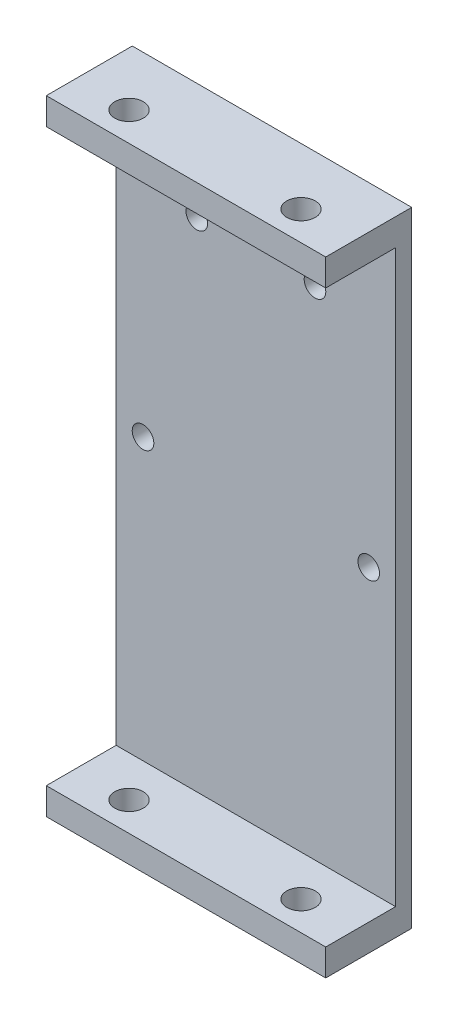
SolidWorks part; units mm, degrees
ref_plane "Front Plane" through (0, 0, 0) normal (0, 0, 1) x (1, 0, 0)
ref_plane "Top Plane" through (0, 0, 0) normal (0, 1, 0) x (1, 0, 0)
ref_plane "Right Plane" through (0, 0, 0) normal (1, 0, 0) x (0, 0, -1)
sketch "Sketch1" plane through (0, 0, 0) normal (0, 0, 1) x (1, 0, 0)
  line L0 (66.04, 78.728) -> (66.04, 66.282) construction
  line L1 (0, 0) -> (66.04, 0)
  line L2 (0, 0) -> (0, 147.574)
  line L3 (0, 147.574) -> (66.04, 147.574)
  line L4 (66.04, 0) -> (66.04, 147.574)
  dimension "D2" = 147.574
extrude "Boss-Extrude1" add sketch "Sketch1" along normal blind 3.81
sketch "Sketch3" plane through (0, 0, 3.81) normal (0, 0, 1) x (1, 0, 0)
  line L0 (66.04, 0) -> (66.04, 147.574) construction
  line L1 (0, 147.574) -> (66.04, 147.574)
  line L2 (0, 147.574) -> (0, 141.224)
  line L3 (0, 141.224) -> (66.04, 141.224)
  line L4 (66.04, 147.574) -> (66.04, 141.224)
  line L6 (0, 0) -> (66.04, 0)
  line L7 (0, 0) -> (0, 6.35)
  line L8 (0, 6.35) -> (66.04, 6.35)
  line L9 (66.04, 0) -> (66.04, 6.35)
  dimension "D1" = 6.35
  dimension "D2" = 6.35
extrude "Boss-Extrude2" add sketch "Sketch3" along normal blind 16.51
sketch "Sketch4" plane through (0, 0, 0) normal (0, -1, 0) x (1, 0, 0)
  line L0 (0, 20.32) -> (66.04, 20.32) construction
  line L3 (0, 20.32) -> (0, 0) construction
  circle A0 centre (12.7, 13.462) radius 3.3782
  circle A5 centre (53.34, 13.462) radius 3.3782
  dimension "D2" = 6.7564
  dimension "D3" = 6.7564
  dimension "D4" = 6.858
  dimension "D6" = 6.858
  dimension "D1" = 40.64
  dimension "D5" = 12.7
extrude "Cut-Extrude1" cut sketch "Sketch4" against normal through all
sketch "Sketch5" plane through (0, 0, 3.81) normal (0, 0, 1) x (1, 0, 0)
  circle A0 centre (46.99, 123.94) radius 2.5527 construction
  circle A1 centre (19.05, 123.94) radius 2.5527 construction
  circle A2 centre (6.35, 72.632) radius 2.5527 construction
  circle A3 centre (59.69, 72.632) radius 2.5527 construction
  circle A4 centre (46.99, 123.94) radius 2.5527
  circle A5 centre (19.05, 123.94) radius 2.5527
  circle A6 centre (6.35, 72.632) radius 2.5527
  circle A7 centre (59.69, 72.632) radius 2.5527
extrude "Cut-Extrude2" cut sketch "Sketch5" against normal up to surface (3.81 mm away) up to face at (33.02, 73.787, 0)
